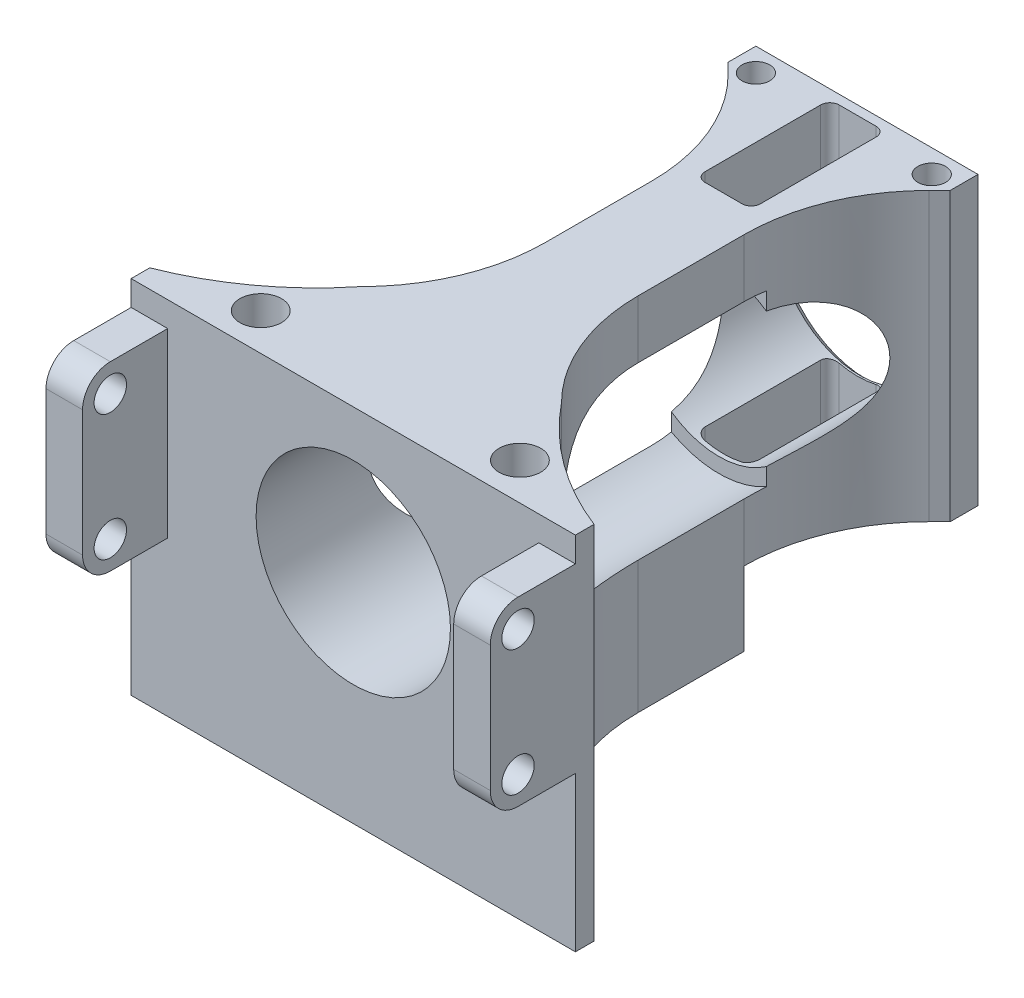
SolidWorks part; units mm, degrees
material "6061 合金"
ref_plane "前视基准面" through (0, 0, 0) normal (0, 0, 1) x (1, 0, 0)
ref_plane "上视基准面" through (0, 0, 0) normal (0, 1, 0) x (1, 0, 0)
ref_plane "右视基准面" through (0, 0, 0) normal (1, 0, 0) x (0, 0, -1)
sketch "草图1" plane through (0, 0, 0) normal (0, 0, 1) x (1, 0, 0)
  line L1 (-24, -15.5) -> (24, -15.5)
  line L2 (-24, -15.5) -> (-24, 15.5)
  line L3 (-24, 15.5) -> (24, 15.5)
  line L4 (24, -15.5) -> (24, 15.5)
  line L5 (-24, -15.5) -> (24, 15.5) construction
  line L6 (-24, 15.5) -> (24, -15.5) construction
  circle A0 centre (0, 0) radius 8.9
  point P0 (0, 0)
  dimension "D3" = 17.8
  dimension "D1" = 48
  dimension "D2" = 31
extrude "凸台-拉伸1" add sketch "草图1" along normal blind 65
sketch "草图2" plane through (0, 0, 65) normal (0, 0, 1) x (1, 0, 0)
  circle A0 centre (0, 0) radius 10.5
  dimension "D1" = 21
extrude "切除-拉伸1" cut sketch "草图2" against normal offset from surface (49 mm away) 16 up to face at (0, 0, 0)
sketch "草图4" plane through (0, 15.5, 0) normal (0, 1, 0) x (1, 0, 0)
  line L0 (-24, 9) -> (-10.8579, -4.1421)
  line L1 (-24, -65) -> (-24, 0) construction
  line L2 (-5, -18.2843) -> (-5, -29.7157)
  line L3 (-10.8579, -43.8579) -> (-24, -57) construction
  line L4 (-24, -57) -> (-24, 9) construction
  line L5 (0, 0) -> (0, -65) construction
  line L6 (24, -65) -> (-24, -65) construction
  line L7 (-24, -65) -> (-24, -62) construction
  line L8 (-24, -62) -> (-21, -62) construction
  line L9 (24, 0) -> (-24, 0) construction
  line L10 (10.8579, -43.8579) -> (24, -57) construction
  line L11 (5, -18.2843) -> (5, -29.7157)
  line L12 (24, 9) -> (10.8579, -4.1421)
  line L13 (24, -57) -> (24, 9) construction
  line L14 (35.5, -24) -> (-35.5, -24) construction
  line L15 (9.5, -2.5) -> (-9.5, -2.5) construction
  line L16 (24, -53.4842) -> (24, 9)
  line L17 (-24, -53.4842) -> (-24, 9)
  arc A2 (5, -18.2843) -> (10.8579, -4.1421) centre (25, -18.2843) cw
  arc A3 (10.8579, -43.8579) -> (5, -29.7157) centre (25, -29.7157) cw
  arc A4 (-5, -29.7157) -> (-10.8579, -43.8579) centre (-25, -29.7157) cw
  arc A5 (-10.8579, -4.1421) -> (-5, -18.2843) centre (-25, -18.2843) cw
  circle A6 centre (-35.5, -24) radius 30 construction
  circle A7 centre (35.5, -24) radius 30 construction
  circle A8 centre (9.5, -2.5) radius 1.2 construction
  circle A9 centre (-9.5, -2.5) radius 1.2 construction
  arc A10 (-10.8579, -43.8579) -> (-24, -53.4842) centre (-35.5, -24) cw
  arc A11 (10.8579, -43.8579) -> (24, -53.4842) centre (35.5, -24) ccw
  point P12 (-5, -24)
  point P26 (5, -10)
  point P29 (5, -38)
  point P32 (-5, -38)
  point P35 (-5, -10)
  point P36 (0, -24)
  point P41 (0, -2.5)
  dimension "D3" = 24
  dimension "D7" = 20
  dimension "D4" = 60
  dimension "D11" = 2.4
  dimension "D1" = 3
  dimension "D2" = 3
  dimension "D5" = 10
  dimension "D6" = 10
  dimension "D8" = 71
  dimension "D9" = 2.5
  dimension "D10" = 19
  dimension "D12" = 135
extrude "切除-拉伸3" cut sketch "草图4" against normal through all
sketch "草图6" plane through (0, 15.5, 0) normal (0, 1, 0) x (1, 0, 0)
  line L0 (0, 0) -> (0, -1) construction
  line L1 (-2, -1) -> (2, -1)
  line L2 (-3, -2) -> (-3, -14.5)
  line L3 (-2, -15.5) -> (2, -15.5)
  line L4 (3, -2) -> (3, -14.5)
  arc A0 (-3, -14.5) -> (-2, -15.5) centre (-2, -14.5) ccw
  arc A1 (2, -15.5) -> (3, -14.5) centre (2, -14.5) ccw
  arc A2 (2, -1) -> (3, -2) centre (2, -2) cw
  arc A3 (-2, -1) -> (-3, -2) centre (-2, -2) ccw
  point P9 (-3, -15.5)
  point P14 (3, -1)
  point P17 (-3, -1)
  dimension "D4" = 1
  dimension "D1" = 1
  dimension "D2" = 14.5
  dimension "D3" = 6
extrude "切除-拉伸5" cut sketch "草图6" along normal through all from surface starting at face at (0, -15.5, 30.7635)
sketch "草图9" plane through (0, 15.5, 0) normal (0, 1, 0) x (1, 0, 0)
  line L0 (9.5, -2.5) -> (-9.5, -2.5) construction
  line L1 (0, -2.5) -> (0, 0) construction
  circle A0 centre (9.5, -2.5) radius 1.5
  circle A1 centre (-9.5, -2.5) radius 1.5
  dimension "D3" = 3
  dimension "D1" = 2.5
  dimension "D2" = 19
extrude "切除-拉伸6" cut sketch "草图9" against normal blind 7
cosmetic thread "装饰螺纹线1" parameters "D2"=3
cosmetic thread "装饰螺纹线2" parameters "D2"=3
extrude "切除-拉伸7" cut sketch "草图9<2>" along normal blind 7 from surface starting at face at (0, -15.5, 8.25)
sketch "草图9<2>" plane through (0, 15.5, 0) normal (0, 1, 0) x (1, 0, 0) same geometry as "草图9"
cosmetic thread "装饰螺纹线3" parameters "D2"=3
cosmetic thread "装饰螺纹线4" parameters "D2"=3
sketch "草图12" plane through (0, -15.5, 0) normal (0, -1, 0) x (1, 0, 0)
  line L0 (-5, 18.2843) -> (5, 18.2843)
  line L12 (-15, 0) -> (15, 0)
  line L14 (15, 0) -> (10.8579, 4.1421)
  line L15 (5, 18.2843) -> (5, 29.7157)
  line L17 (24, 53.4842) -> (24, 65)
  line L18 (24, 65) -> (-24, 65)
  line L19 (-24, 65) -> (-24, 53.4842)
  line L21 (-5, 29.7157) -> (-5, 18.2843)
  line L22 (-10.8579, 4.1421) -> (-15, 0)
  line L24 (-15, 0) -> (15, 0) construction
  line L26 (15, 0) -> (10.8579, 4.1421) construction
  line L27 (5, 18.2843) -> (5, 29.7157)
  line L29 (24, 53.4842) -> (24, 65)
  line L30 (24, 65) -> (-24, 65)
  line L31 (-24, 65) -> (-24, 53.4842)
  line L33 (-5, 29.7157) -> (-5, 18.2843)
  line L34 (-10.8579, 4.1421) -> (-15, 0) construction
  arc A4 (5, 18.2843) -> (10.8579, 4.1421) centre (25, 18.2843) ccw
  arc A5 (10.8579, 43.8579) -> (5, 29.7157) centre (25, 29.7157) ccw
  arc A6 (-5, 29.7157) -> (-10.8579, 43.8579) centre (-25, 29.7157) ccw
  arc A7 (-10.8579, 4.1421) -> (-5, 18.2843) centre (-25, 18.2843) ccw
  arc A8 (5, 18.2843) -> (10.8579, 4.1421) centre (25, 18.2843) ccw construction
  arc A9 (10.8579, 43.8579) -> (5, 29.7157) centre (25, 29.7157) ccw
  arc A10 (-5, 29.7157) -> (-10.8579, 43.8579) centre (-25, 29.7157) ccw
  arc A11 (-10.8579, 4.1421) -> (-5, 18.2843) centre (-25, 18.2843) ccw construction
  arc A14 (24, 53.4842) -> (10.8579, 43.8579) centre (35.5, 24) ccw
  arc A15 (24, 53.4842) -> (10.8579, 43.8579) centre (35.5, 24) ccw
  arc A16 (-10.8579, 43.8579) -> (-24, 53.4842) centre (-35.5, 24) ccw
  arc A17 (-10.8579, 43.8579) -> (-24, 53.4842) centre (-35.5, 24) ccw
  dimension "D1" = 0
extrude "凸台-拉伸4" add sketch "草图12" along normal blind 8
sketch "草图11" plane through (0, 15.5, 0) normal (0, 1, 0) x (1, 0, 0)
  line L0 (14, -51.5) -> (-14, -51.5) construction
  line L1 (0, -51.5) -> (0, 0) construction
  circle A0 centre (14, -51.5) radius 2.25
  circle A1 centre (-14, -51.5) radius 2.25
  dimension "D3" = 4.5
  dimension "D1" = 51.5
  dimension "D2" = 28
extrude "切除-拉伸9" cut sketch "草图11" against normal through all
sketch "草图14" plane through (0, -23.5, 0) normal (0, -1, 0) x (1, 0, 0)
  line L0 (-5, 24) -> (5, 24) construction
  line L1 (-5, 29.7157) -> (-5, 18.2843) construction
  line L2 (5, 18.2843) -> (5, 29.7157) construction
  circle A0 centre (0, 24) radius 1.5
  dimension "D1" = 3
extrude "切除-拉伸10" cut sketch "草图14" against normal blind 11
cosmetic thread "装饰螺纹线9" parameters "D2"=4
sketch "草图15" plane through (0, 15.5, 0) normal (0, 1, 0) x (1, 0, 0)
  line L0 (24, -65) -> (-24, -65) construction
  line L1 (20.05, -65) -> (-20.05, -65)
  line L2 (20.05, -65) -> (20.05, -55.5)
  line L3 (20.05, -55.5) -> (-20.05, -55.5)
  line L4 (-20.05, -65) -> (-20.05, -55.5)
  line L5 (0, 0) -> (0, -55.5) construction
  circle A0 centre (-14, -51.5) radius 2.25 construction
  dimension "D1" = 40.1
  dimension "D2" = 4
extrude "切除-拉伸11" cut sketch "草图15" against normal through all
sketch "草图17" plane through (24, 0, 0) normal (1, 0, 0) x (0, 0, -1)
  line L0 (-53.4842, -23.5) -> (-65, -23.5) construction
  line L1 (-65, 15.5) -> (-53.4842, 15.5) construction
  line L2 (-61.7, 9.8) -> (-61.7, -3.8) construction
  line L3 (-61.7, 3) -> (-55.5, 3) construction
  line L4 (-55.5, -23.5) -> (-55.5, -6.8)
  line L5 (-55.5, -6.8) -> (-61.7, -6.8)
  line L6 (-64.7, -3.8) -> (-64.7, 9.8)
  line L9 (-64.7, 15.5) -> (-94.5, 15.5)
  line L10 (-94.5, 15.5) -> (-94.5, -23.5)
  line L11 (-94.5, -23.5) -> (-55.5, -23.5)
  line L12 (-55.5, -23.5) -> (-55.5, 15.5) construction
  line L13 (-61.7, 12.8) -> (-55.5, 12.8)
  line L14 (-55.5, 12.8) -> (-55.5, 15.5)
  line L15 (-55.5, 15.5) -> (-64.7, 15.5)
  circle A0 centre (-61.7, 9.8) radius 1.75
  circle A1 centre (-61.7, -3.8) radius 1.75
  arc A3 (-61.7, -6.8) -> (-64.7, -3.8) centre (-61.7, -3.8) cw
  arc A4 (-61.7, 12.8) -> (-64.7, 9.8) centre (-61.7, 9.8) ccw
  dimension "D3" = 3.5
  dimension "D4" = 3
  dimension "D1" = 13.6
  dimension "D2" = 6.2
  dimension "D6" = 12.5
extrude "切除-拉伸13" cut sketch "草图17" against normal through all
sketch "草图19" plane through (0, -15.5, 0) normal (0, -1, 0) x (1, 0, 0)
  line L0 (-10.8579, 4.1421) -> (-15, 0) construction
  line L1 (-15, 0) -> (-12, 0)
  line L2 (-15, 0) -> (-15, 3)
  line L3 (-15, 3) -> (-12, 3)
  line L4 (-12, 0) -> (-12, 3)
  line L5 (15, 0) -> (10.8579, 4.1421) construction
  line L6 (15, 0) -> (12, 0)
  line L7 (15, 0) -> (15, 3)
  line L8 (15, 3) -> (12, 3)
  line L9 (12, 0) -> (12, 3)
  dimension "D1" = 3
extrude "切除-拉伸14" cut sketch "草图19" against normal through all
chamfer "倒角1" distance 0.8 angle 45 1 edges at (8.9, 0, 0)
